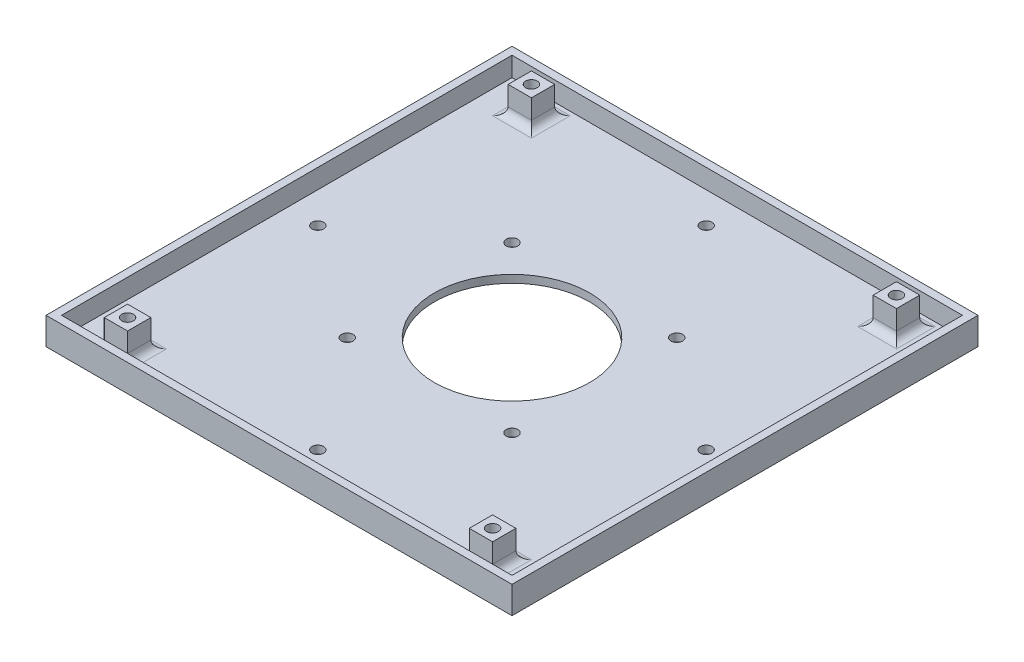
SolidWorks part; units mm, degrees
ref_plane "Front Plane" through (0, 0, 0) normal (0, 0, 1) x (1, 0, 0)
ref_plane "Top Plane" through (0, 0, 0) normal (0, 1, 0) x (1, 0, 0)
ref_plane "Right Plane" through (0, 0, 0) normal (1, 0, 0) x (0, 0, -1)
sketch "Sketch1" plane through (0, 0, 0) normal (0, 1, 0) x (1, 0, 0)
  line L0 (-60, 60) -> (-60, -60)
  line L1 (58, 58) -> (-58, 58)
  line L2 (58, 58) -> (58, -58)
  line L3 (58, -58) -> (-58, -58)
  line L4 (-58, 58) -> (-58, -58)
  line L5 (58, 58) -> (-58, -58) construction
  line L6 (58, -58) -> (-58, 58) construction
  line L7 (60, -60) -> (-60, -60)
  line L8 (60, 60) -> (60, -60)
  line L9 (60, 60) -> (-60, 60)
  circle A0 centre (0, 0) radius 20
  circle A1 centre (21.2132, 21.2132) radius 1.5
  circle A2 centre (-21.2132, -21.2132) radius 1.5
  circle A3 centre (-21.2132, 21.2132) radius 1.5
  circle A4 centre (21.2132, -21.2132) radius 1.5
  point P0 (0, 0)
  dimension "D1" = 40
  dimension "D2" = 3
  dimension "D3" = 30
  dimension "D6" = 3
  dimension "D7" = 30
  dimension "D4" = 116
  dimension "D5" = 116
  dimension "D8" = 2
extrude "Boss-Extrude1" add sketch "Sketch1" along normal blind 2 contours L1 L4 L3 L2 A2 A1 A0 A3 A4 region at (56.3595, 0, 0)
sketch "Sketch2" plane through (0, 2, 0) normal (0, 1, 0) x (1, 0, 0)
  line L0 (0, 0) -> (0, -85.9982) construction
  line L1 (50, 49) -> (-50, 49)
  line L2 (50, 49) -> (50, -49)
  line L3 (50, -49) -> (-50, -49)
  line L4 (-50, 49) -> (-50, -49)
  line L5 (50, 49) -> (-50, -49) construction
  line L6 (50, -49) -> (-50, 49) construction
  line L7 (-50, -49) -> (-44, -49)
  line L8 (-50, -49) -> (-50, -55)
  line L9 (-50, -55) -> (-44, -55)
  line L10 (-44, -49) -> (-44, -55)
  line L11 (0, 0) -> (-70.7308, 0) construction
  line L12 (-47, -55) -> (-47, -41.6244) construction
  line L13 (-50, -52) -> (-32.7126, -52) construction
  line L14 (-44, 49) -> (-44, 55)
  line L15 (-50, 55) -> (-44, 55)
  line L16 (-50, 49) -> (-50, 55)
  line L17 (-50, 49) -> (-44, 49)
  line L18 (50, 49) -> (50, 55)
  line L19 (44, 49) -> (44, 55)
  line L20 (50, 55) -> (44, 55)
  line L21 (50, -52) -> (32.7126, -52) construction
  line L22 (47, -55) -> (47, -41.6244) construction
  line L23 (44, -49) -> (44, -55)
  line L24 (50, -55) -> (44, -55)
  line L25 (50, -49) -> (50, -55)
  circle A0 centre (-47, -52) radius 1.5
  circle A1 centre (-47, 52) radius 1.5
  circle A2 centre (47, 52) radius 1.5
  circle A3 centre (47, -52) radius 1.5
  point P0 (0, 0)
  dimension "D5" = 3
  dimension "D1" = 98
  dimension "D2" = 100
  dimension "D3" = 6
  dimension "D4" = 6
extrude "Boss-Extrude2" add sketch "Sketch2" along normal blind 7 contours L10 L3 L8 L9 A0 | L25 L3 L23 L24 A3 | L18 L20 L19 L1 A2 | L16 L1 L14 L15 A1 region at (47, 2, -49.0849) region at (49.9151, 2, 52) region at (-47, 2, -49.0849) region at (-44.0849, 2, 52)
extrude "Boss-Extrude3" add sketch "Sketch1<4>" along normal blind 7 contours L8 L9 L0 L7 L4 L1 L2 L3 region at (0, 0, -58.3029)
sketch "Sketch1<4>" plane through (0, 0, 0) normal (0, 1, 0) x (1, 0, 0) same geometry as "Sketch1"
sketch "Sketch3" plane through (0, 2, 0) normal (0, 1, 0) x (1, 0, 0)
  line L0 (0, 0) -> (94.3703, 0) construction
  line L1 (0, 0) -> (-83.2282, 0) construction
  line L2 (0, 0) -> (0, -82.7836) construction
  line L3 (0, 0) -> (0, 64.6802) construction
  circle A0 centre (50, 0) radius 1.5
  circle A1 centre (-50, 0) radius 1.5
  circle A2 centre (0, -50) radius 1.5
  circle A3 centre (0, 50) radius 1.5
  dimension "D1" = 3
  dimension "D2" = 50
  dimension "D3" = 3
  dimension "D4" = 50
extrude "Cut-Extrude1" cut sketch "Sketch3" against normal through all
fillet "Fillet2" radius 2 16 edges at (-47, 2, 49) (-50, 2, 52) (-47, 2, 55) (-44, 2, 52) (50, 2, 52) (47, 2, 55) (47, 2, 49) (44, 2, 52) (47, 2, -55) (44, 2, -52) (47, 2, -49) (50, 2, -52) (-47, 2, -55) (-44, 2, -52) (-50, 2, -52) (-47, 2, -49)
